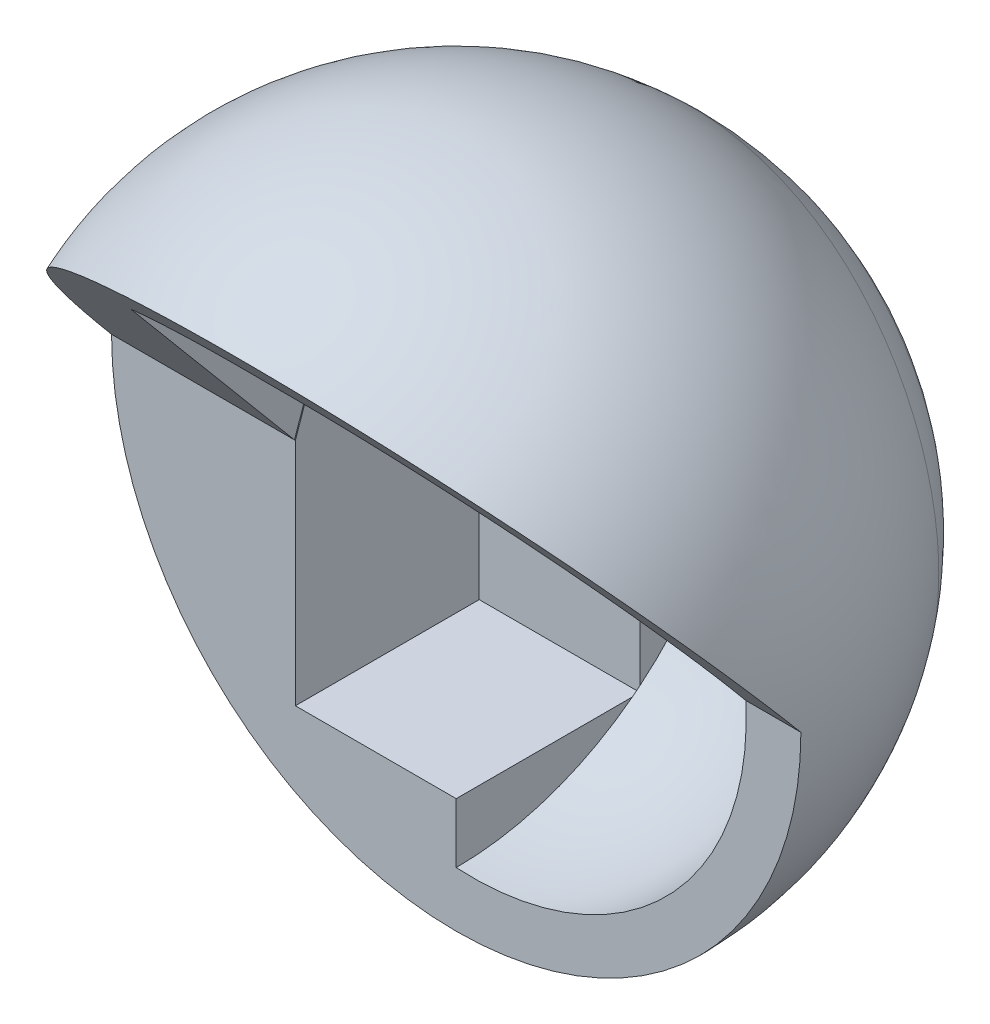
SolidWorks part; units mm, degrees
ref_plane "Front Plane" through (0, 0, 0) normal (0, 0, 1) x (1, 0, 0)
ref_plane "Top Plane" through (0, 0, 0) normal (0, 1, 0) x (1, 0, 0)
ref_plane "Right Plane" through (0, 0, 0) normal (1, 0, 0) x (0, 0, -1)
ref_axis "Axis1" through (0, 29.5432, 0) along (0, -1, 0)
sketch "Sketch3" plane through (0, 0, 0) normal (0, 0, 1) x (1, 0, 0)
  line L5 (19.05, 0) -> (-19.05, 0)
  arc A1 (-19.05, 0) -> (0, -19.05) centre (0, 0) ccw
  arc A2 (19.05, 0) -> (0, -19.05) centre (0, 0) cw
revolve "Revolve4" add sketch "Sketch3" angle 220 about L5 reverse direction yes
sketch "Sketch10" plane through (0, 0, 0) normal (0, -0.6428, 0.766) x (1, 0, 0)
  line L1 (0, 0) -> (0, 16.002)
  line L2 (0, 0) -> (16.002, 0)
  line L3 (19.05, 0) -> (-19.05, 0) construction
  arc A3 (16.002, 0) -> (0, 16.002) centre (0.8908, 0.8908) ccw
  arc A4 (19.05, 0) -> (-19.05, 0) centre (0, 0) ccw construction
  point P4 (0, 0)
  point P14 (0, 19.05)
  dimension "D1" = 3.048
  dimension "D2" = 3.048
revolve "Cut-Revolve1" cut sketch "Sketch10" angle 234 about L2 reverse direction yes
sketch "Sketch11" plane through (0, 0, 0) normal (0, 0, 1) x (1, 0, 0)
  line L11 (0, 12.7) -> (-8.89, 12.7)
  line L12 (0, 12.7) -> (0, -12.7)
  line L13 (0, -12.7) -> (-8.89, -12.7)
  line L14 (-8.89, 12.7) -> (-8.89, -12.7)
  point P4 (0, 0)
  dimension "D1" = 25.4
  dimension "D2" = 8.89
extrude "Cut-Extrude3" cut sketch "Sketch11" against normal blind 10.16
sketch "Sketch12" plane through (0, 0, 0) normal (0, -0.6428, 0.766) x (1, 0, 0)
  line L0 (-8.9389, 0) -> (-8.9389, 14.0911)
  line L1 (0, 0) -> (-8.9389, 0)
  line L2 (0, 0) -> (0, 16.002)
  arc A0 (0, 16.002) -> (-8.9389, 14.0911) centre (-1.4466, 0.9064) ccw
revolve "Cut-Revolve2" cut sketch "Sketch12" angle 59 about L1
ref_plane "Plane1" through (0, 0, -19.05) normal (0, 0, 1) x (1, 0, 0)
sketch "Sketch14" plane through (0, 0, -19.05) normal (0, 0, 1) x (1, 0, 0)
  line L0 (0, 12.3628) -> (0, -12.3628) construction
  ellipse E0 centre (0, 0) end of major axis (15.24, 0) minor radius 13.97
  ellipse E1 centre (0, 0) end of major axis (12.7, 0) minor radius 11.43
split line "Split Line1"
